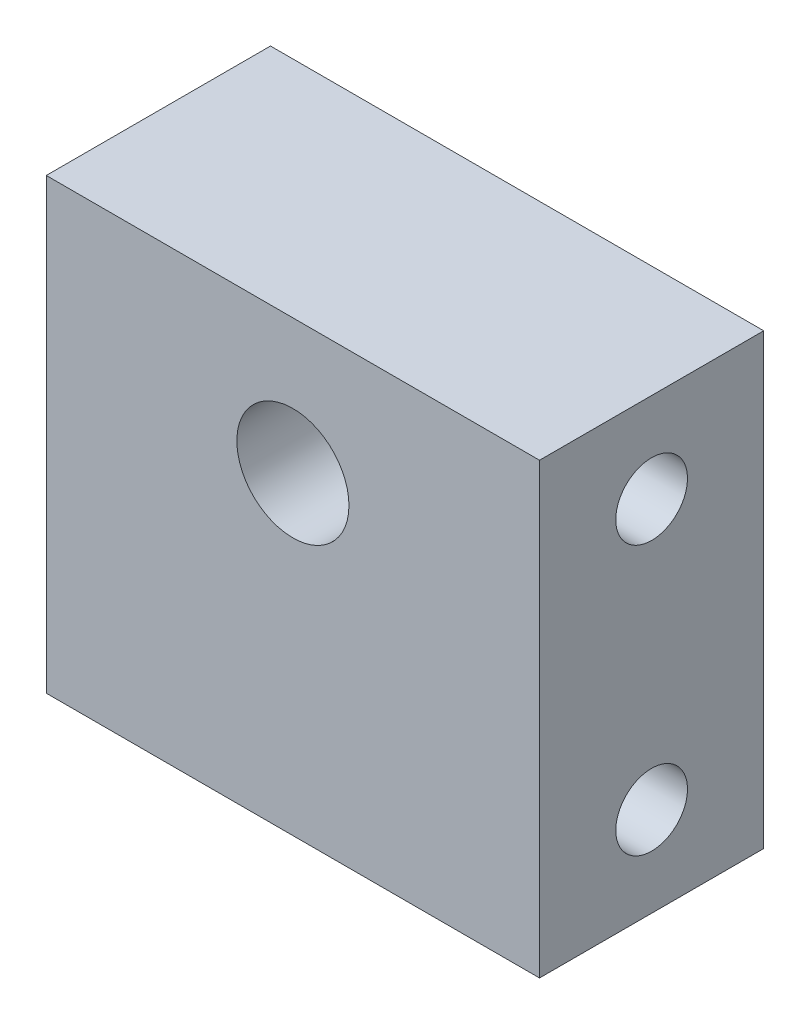
SolidWorks part; units mm, degrees
material "AISI 4130 Acier normalisé à 870C"
ref_plane "Plan de face" through (0, 0, 0) normal (0, 0, 1) x (1, 0, 0)
ref_plane "Plan de dessus" through (0, 0, 0) normal (0, 1, 0) x (1, 0, 0)
ref_plane "Plan de droite" through (0, 0, 0) normal (1, 0, 0) x (0, 0, -1)
sketch "Esquisse1" plane through (0, 0, 0) normal (0, 0, 1) x (1, 0, 0)
  line L1 (0, 0) -> (11, 0)
  line L2 (0, 0) -> (0, 10)
  line L3 (0, 10) -> (11, 10)
  line L4 (11, 0) -> (11, 10)
  dimension "D1" = 11
  dimension "D2" = 10
extrude "Boss.-Extru.1" add sketch "Esquisse1" along normal blind 5
hole_wizard "Trou pour taraudage pour trou taraudé M21" positions "Esquisse2" profile "Esquisse4" hole size "M2" standard "ISO" end condition through all
sketch "Esquisse2" plane through (0, 0, 0) normal (-1, 0, 0) x (0, 0, 1)
  line L4 (2.5, 8) -> (2.5, 7.5239) construction
  line L6 (0, 10) -> (0, 0) construction
  line L7 (5, 10) -> (5, 0) construction
  line L8 (5, 10) -> (0, 10) construction
  line L9 (0, 5) -> (3.912, 5) construction
  point P0 (2.5, 8)
  point P21 (2.5, 10)
  point P22 (2.5, 2)
  dimension "D1" = 2
sketch "Esquisse4" plane through (0, 8, 2.5) normal (0, 1, 0) x (0, 0, 1)
  line L0 (0, 0) -> (0, 11)
  line L1 (0, 11) -> (0.8, 11)
  line L2 (0.8, 11) -> (0.8, 0)
  line L5 (0.8, 0) -> (0, 0)
  line L11 (0, -6.35) -> (0, 107.95) construction
  dimension "Diamètre du perçage jusqu'au prochain" = 1.6
  dimension "Profondeur du perçage jusqu'au prochain" = 11
hole_wizard "Trou pour taraudage pour trou taraudé M32" positions "Esquisse5" profile "Esquisse6" hole size "M3" standard "ISO" end condition through all
sketch "Esquisse5" plane through (0, 0, 5) normal (0, 0, 1) x (1, 0, 0)
  line L0 (5.5, 10) -> (5.5, 4.339) construction
  line L1 (11, 10) -> (0, 10) construction
  point P0 (5.5, 7)
  dimension "D1" = 3
sketch "Esquisse6" plane through (5.5, 7, 5) normal (1, 0, 0) x (0, -1, 0)
  line L0 (0, 0) -> (0, 5)
  line L1 (0, 5) -> (1.25, 5)
  line L2 (1.25, 5) -> (1.25, 0)
  line L5 (1.25, 0) -> (0, 0)
  line L11 (0, -6.35) -> (0, 107.95) construction
  dimension "Diamètre du perçage jusqu'au prochain" = 2.5
  dimension "Profondeur du perçage jusqu'au prochain" = 5
